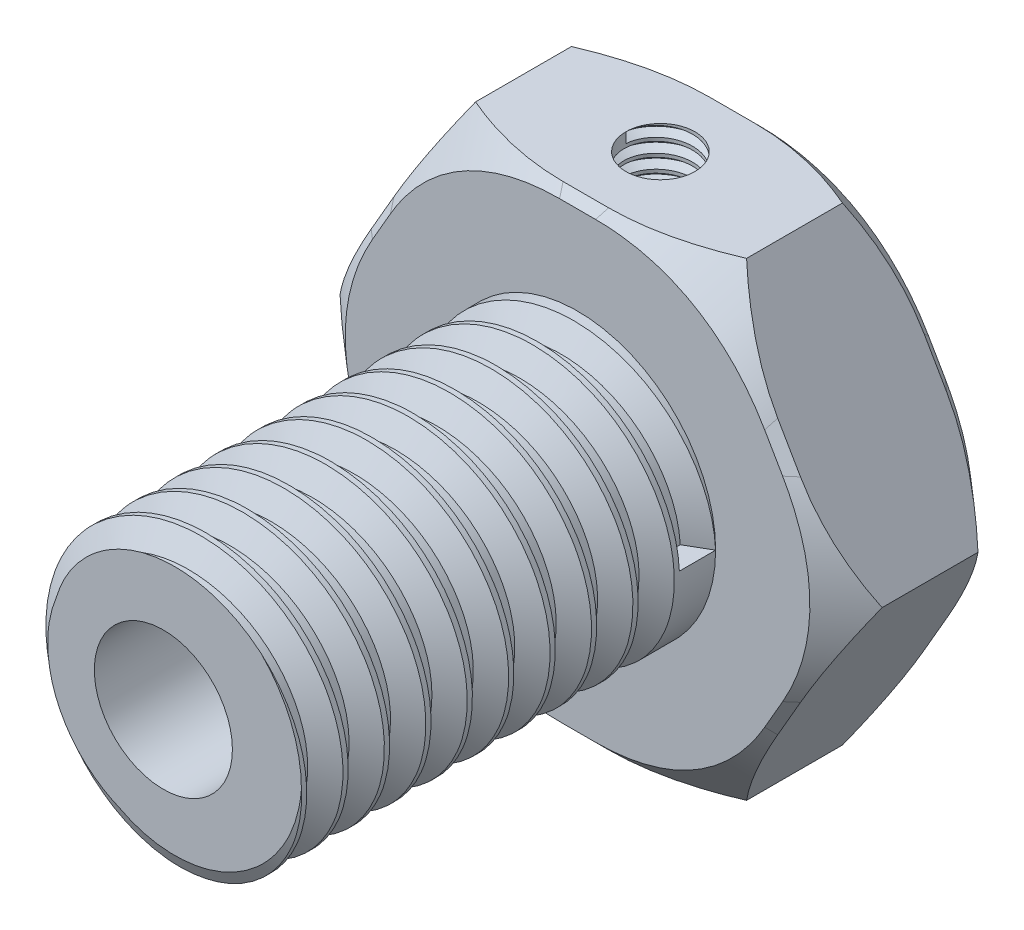
SolidWorks part; units mm, degrees
material "1.0570 (S355J2G3)"
ref_plane "Front" through (0, 0, 0) normal (0, 0, 1) x (1, 0, 0)
ref_plane "Top" through (0, 0, 0) normal (0, 1, 0) x (1, 0, 0)
ref_plane "Right" through (0, 0, 0) normal (1, 0, 0) x (0, 0, -1)
sketch "Sketch1" plane through (0, 0, 0) normal (0, 0, 1) x (1, 0, 0)
  line L1 (4.9075, -8.5) -> (9.815, 0)
  line L2 (9.815, 0) -> (4.9075, 8.5)
  line L3 (4.9075, 8.5) -> (-4.9075, 8.5)
  line L4 (-4.9075, 8.5) -> (-9.815, 0)
  line L5 (-9.815, 0) -> (-4.9075, -8.5)
  line L6 (-4.9075, -8.5) -> (4.9075, -8.5)
  circle A0 centre (0, 0) radius 8.5 construction
  dimension "D1" = 17
extrude "Boss-Extrude1" add sketch "Sketch1" along normal blind 6
sketch "Sketch2" plane through (0, 0, 6) normal (0, 0, 1) x (1, 0, 0)
  circle A0 centre (0, 0) radius 5
  dimension "D1" = 10
extrude "Boss-Extrude2" add sketch "Sketch2" along normal blind 15
thread "Thread1" pitch 1.5 start angle 0, offset 0, length 0, pitch 1.5, diameter 10
ref_plane "Plane1" through (5, 0, 6) normal (0, -1, 0) x (1, 0, 0)
sketch "Thread Profile1" plane through (5, 0, 6) normal (0, -1, 0) x (1, 0, 0)
  line L0 (0, 0) -> (0, 1.5) construction
  line L11 (0, 0) -> (0, 1.3125)
  line L12 (0, 1.3125) -> (-0.8119, 0.8437)
  line L13 (-0.8119, 0.8437) -> (-0.8119, 0.4687)
  line L15 (-0.8119, 0.4687) -> (0, 0)
  line L17 (-0.8119, 0.6562) -> (0, 0.6562) construction
  point P2 (0, 0)
  dimension "Pitch" = 1.5
  dimension "Profile_Angle" = 60
  dimension "Profile_Land" = 0.375
  dimension "Profile_Height" = 0.8119
chamfer "Chamfer1" distance 0.4 angle 45 6 edges at (7.3612, -4.25, 0) (7.3612, 4.25, 0) (0, 8.5, 0) (-7.3612, 4.25, 0) (-7.3612, -4.25, 0) (0, -8.5, 0)
fillet "Fillet1" radius 10 6 edges at (4.792, 8.3, 0.2) (9.584, 0, 0.2) (4.792, -8.3, 0.2) (-4.792, -8.3, 0.2) (-9.584, 0, 0.2) (-4.792, 8.3, 0.2)
chamfer "Chamfer2" distance 0.3 angle 45 6 edges at (-7.3612, 4.25, 6) (-7.3612, -4.25, 6) (0, -8.5, 6) (7.3612, -4.25, 6) (7.3612, 4.25, 6) (0, 8.5, 6)
fillet "Fillet2" radius 10 6 edges at (-9.6417, 0, 5.85) (-4.8209, -8.35, 5.85) (4.8209, -8.35, 5.85) (9.6417, 0, 5.85) (4.8209, 8.35, 5.85) (-4.8209, 8.35, 5.85)
sketch "Sketch6" plane through (0, 0, 0) normal (0, 0, -1) x (-1, 0, 0)
  circle A0 centre (0, 0) radius 2.5
  dimension "D1" = 5
extrude "Cut-Extrude1" cut sketch "Sketch6" against normal up to surface (21 mm away) up to face at (0.5884, 0.1682, 21)
chamfer "Chamfer3" distance 0.5 angle 45 1 edges at (-2.5, 0, 0)
hole_wizard "Tap Drill Slot for M3 Tap1" positions "Sketch12" profile "Sketch13" size "M3" standard "ISO" slot yes
sketch "Sketch12" plane through (0, 8.5, 0) normal (0, 1, 0) x (1, 0, 0)
  point P0 (0, -3)
  dimension "D1" = 3
sketch "Sketch13" plane through (0, 8.5, 3) normal (1, 0, 0) x (0, 0, 1)
  line L0 (0, 0) -> (0, 9.2501)
  line L1 (0, 9.2501) -> (1.25, 8.499)
  line L2 (1.25, 8.499) -> (1.25, 0)
  line L5 (1.25, 0) -> (0, 0)
  line L10 (0, 9.2501) -> (-1.25, 8.499) construction
  line L11 (0, -6.35) -> (0, 107.95) construction
  dimension "Hole Dia." = 2.5
  dimension "Hole Depth" = 8.499
  dimension "Drill Angle" = 118
thread "Thread2" pitch 0.5 profile "Thread Profile4" start angle 0, offset 0, length 7, pitch 0.5, diameter 2.5
ref_plane "Plane4" through (-1.25, 8.5, 3) normal (0, 0, 1) x (-1, 0, 0)
sketch "Thread Profile4" plane through (-1.25, 8.5, 3) normal (0, 0, 1) x (-1, 0, 0)
  line L0 (0, 0) -> (0, 0.5) construction
  line L1 (0, 0) -> (0.2706, 0.1562)
  line L2 (0.2706, 0.1562) -> (0.2706, 0.2187)
  line L3 (0.2706, 0.2187) -> (0, 0.375)
  line L4 (0.2706, 0.1875) -> (0, 0.1875) construction
  line L11 (0, 0) -> (0, 0.375)
  point P2 (0, 0)
  dimension "Pitch" = 0.5
  dimension "Profile_Angle" = 60
  dimension "Profile_Land" = 0.0625
  dimension "Profile_Height" = 0.2706
